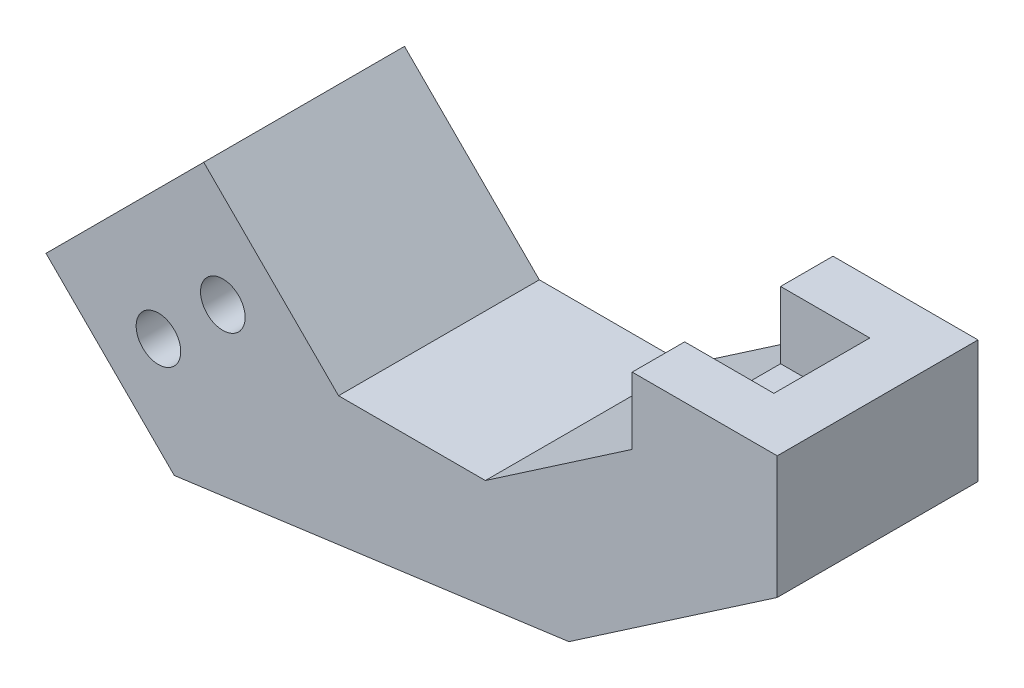
SolidWorks part; units mm, degrees
ref_plane "Front Plane" through (0, 0, 0) normal (0, 0, 1) x (1, 0, 0)
ref_plane "Top Plane" through (0, 0, 0) normal (0, 1, 0) x (1, 0, 0)
ref_plane "Right Plane" through (0, 0, 0) normal (1, 0, 0) x (0, 0, -1)
sketch "Sketch1" plane through (0, 0, 0) normal (0, 0, 1) x (1, 0, 0)
  line L0 (0, 6) -> (5, 6)
  line L1 (5, 6) -> (5, -5)
  line L2 (-13.6758, -17.7681) -> (-49.0563, -22.5563)
  line L4 (-49.0563, -22.5563) -> (-60.5563, -11.0563)
  line L5 (-60.5563, -11.0563) -> (-46.4142, 3.0858)
  line L6 (-46.4142, 3.0858) -> (-34.3284, -9)
  line L7 (-34.3284, -9) -> (-21.1642, -9)
  line L8 (-8, -9) -> (-8, 0) construction
  line L9 (0, 0) -> (-30, 0) construction
  line L10 (-8, 0) -> (0, 0)
  line L11 (0, 0) -> (0, 6)
  line L12 (-39.25, -1.25) -> (-54.8063, -16.8063) construction
  line L13 (-45, 4.5) -> (-46.4142, 3.0858) construction
  line L14 (-33.5, -7) -> (-54.8063, -16.8063) construction
  line L15 (-54.8063, -16.8063) -> (-45, 4.5) construction
  line L16 (-8, 0) -> (-21.1642, -9)
  line L17 (5, -5) -> (-13.6758, -17.7681)
  line L18 (-8, -9) -> (-8, -17) construction
  line L19 (-45, 4.5) -> (-33.5, -7) construction
  line L20 (5, -15.2406) -> (-8, -17) construction
  line L21 (-33.5, -7) -> (-45, 4.5) construction
  line L22 (-8, -17) -> (-13.6758, -17.7681) construction
  line L23 (5, -5) -> (5, -15.2406) construction
  line L24 (-21.1642, -9) -> (-8, -9) construction
  point P23 (-15.6449, -18.0346)
  point P24 (-19.8503, -9)
  point P25 (-19.5676, -9)
  dimension "D1" = 2
  dimension "D2" = 8
  dimension "D3" = 2
  dimension "D4" = 20
  dimension "D5" = 8
  dimension "D6" = 5
  dimension "D7" = 11
extrude "Boss-Extrude1" add sketch "Sketch1" against normal blind 13 and the other way blind 5
sketch "Sketch2" plane through (0, 0, 0) normal (0, 1, 0) x (1, 0, 0)
  circle A0 centre (-3, 3.95) radius 1.5
  circle A1 centre (-3, 3.95) radius 1.5 construction
extrude "Cut-Extrude1" cut sketch "Sketch2" against normal through all
sketch "Sketch3" plane through (0, 0, -13) normal (0, 0, -1) x (-1, 0, 0)
  line L0 (43.2587, -5.7274) -> (46.1451, -8.4966) construction
  line L1 (34.3284, -9) -> (46.4142, 3.0858) construction
  line L2 (60.5563, -11.0563) -> (49.0563, -22.5563) construction
  line L3 (49.0325, -11.2669) -> (51.9189, -14.0361) construction
  line L4 (46.1451, -8.4966) -> (49.0325, -11.2669) construction
  line L5 (51.9189, -14.0361) -> (54.8063, -16.8063) construction
  line L6 (40.3713, -2.9571) -> (43.2587, -5.7274) construction
  circle A0 centre (50.4757, -12.6515) radius 2
  circle A1 centre (44.7019, -7.112) radius 2
  dimension "D1" = 4
extrude "Cut-Extrude2" cut sketch "Sketch3" against normal through all
ref_axis "Axis1" through (-44.7019, -7.112, 5) along (0, 0, -1)
ref_axis "Axis2" through (-50.4757, -12.6515, 5) along (0, 0, -1)
ref_plane "Plane1" through (-17.8726, 18.6286, 0) normal (0.6923, -0.7216, 0) x (-0.7216, -0.6923, 0)
sketch "Sketch4" plane through (0, 0, 0) normal (0, 1, 0) x (1, 0, 0)
  line L0 (0, -5) -> (0, 13) construction
  line L1 (-8, -5) -> (0, -5)
  line L2 (-8, -5) -> (-8, -0.3)
  line L3 (-8, -0.3) -> (0, -0.3)
  line L4 (0, -5) -> (0, -0.3)
  line L5 (0, 0) -> (-30, 0) construction
  line L6 (-8, 13) -> (0, 13)
  line L7 (-8, 13) -> (-8, 8.3)
  line L8 (-8, 8.3) -> (0, 8.3)
  line L9 (0, 13) -> (0, 8.3)
  line L10 (-8, -5) -> (-8, 13) construction
  line L11 (0, -5) -> (-8, -5) construction
  point P14 (-8, 13)
  point P16 (-8, -5)
  dimension "D1" = 0.3
extrude "Boss-Extrude2" add sketch "Sketch4" along normal up to surface (6 mm away) up to face at (2.5, 6, -4)
